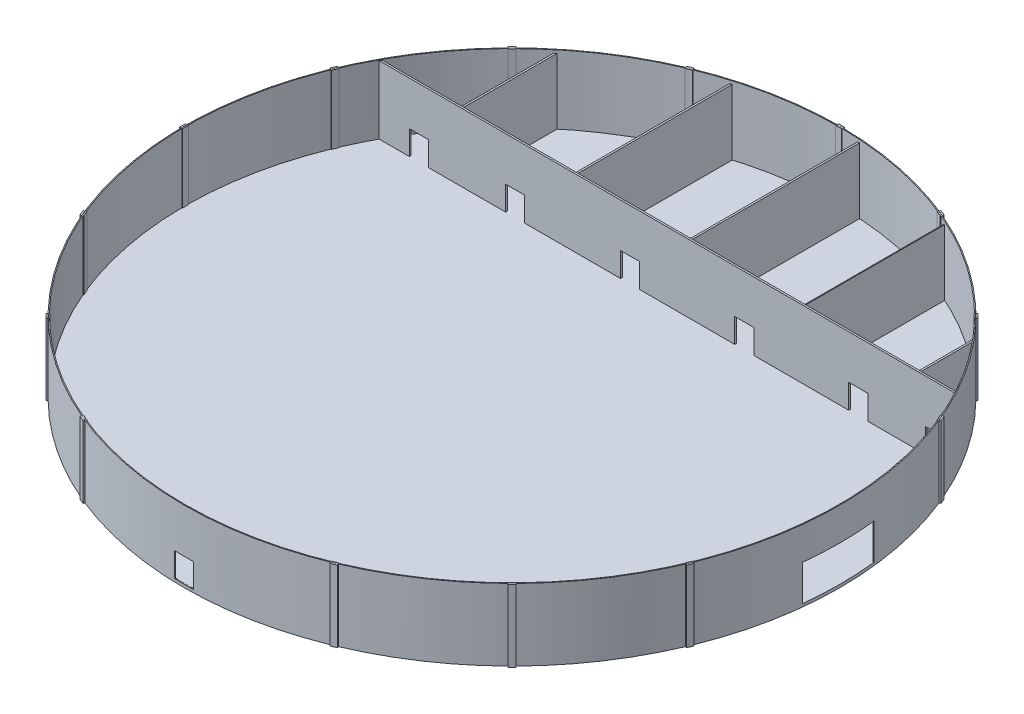
SolidWorks part; units mm, degrees
ref_plane "Front Plane" through (0, 0, 0) normal (0, 0, 1) x (1, 0, 0)
ref_plane "Top Plane" through (0, 0, 0) normal (0, 1, 0) x (1, 0, 0)
ref_plane "Right Plane" through (0, 0, 0) normal (1, 0, 0) x (0, 0, -1)
sketch "Sketch1" plane through (0, 0, 0) normal (0, 1, 0) x (1, 0, 0)
  circle A0 centre (0, 0) radius 27500
  dimension "D1" = 55000
extrude "Boss-Extrude2" add sketch "Sketch1" along normal blind 6000
sketch "Sketch2" plane through (0, 6000, 0) normal (0, 1, 0) x (1, 0, 0)
  circle A2 centre (0, 0) radius 27425
  dimension "D1" = 54850
extrude "Cut-Extrude1" cut sketch "Sketch2" against normal blind 5750
sketch "Sketch3" plane through (0, 0, 0) normal (0, 1, 0) x (1, 0, 0)
ref_plane "Plane1" through (0, 0, 27500) normal (0, 0, 1) x (1, 0, 0)
sketch "Sketch5" plane through (0, 0, 27500) normal (0, 0, 1) x (1, 0, 0)
  line L0 (-808.8037, 252) -> (-808.8037, 2284)
  line L1 (791.1963, 252) -> (791.1963, 2284)
  line L2 (791.1963, 2284) -> (-808.8037, 2284)
  line L3 (-808.8037, 252) -> (791.1963, 252)
  line L4 (-27500, 0) -> (27500, 0) construction
  dimension "D1" = 2032
  dimension "D2" = 2032
  dimension "D3" = 1600
  dimension "D4" = 1600
  dimension "D5" = 252
extrude "Cut-Extrude4" cut sketch "Sketch5" against normal mid plane 2527
sketch "Sketch6" plane through (0, 250, 0) normal (0, 1, 0) x (1, 0, 0)
  line L0 (23976.2032, 13150) -> (24148.0978, 13000)
  line L1 (-24148.0978, 13000) -> (24148.0978, 13000)
  line L2 (-23976.2032, 13150) -> (-24148.0978, 13000)
  line L3 (-23976.2032, 13150) -> (23976.2032, 13150)
sketch "Sketch8" plane through (0, 0, 0) normal (0, 1, 0) x (1, 0, 0)
  line L0 (-7969.0277, 26241.6696) -> (-7969.0277, 13140)
  line L1 (-7817.0277, 26287.3487) -> (-7817.0277, 13150)
  line L2 (-17559.0277, 21066.8263) -> (-17407.0277, 21192.5933)
  line L3 (-17559.0277, 13140) -> (-17559.0277, 21066.8263)
  line L4 (11210.9723, 25028.8778) -> (11210.9723, 13140)
  line L5 (-17407.0277, 13140) -> (-17407.0277, 21192.5933)
  line L6 (20800.9723, 17823.2128) -> (20800.9723, 13140)
  line L7 (-17559.0277, 13140) -> (-17407.0277, 13140)
  line L8 (1620.9723, 27377.0538) -> (1620.9723, 13150)
  line L9 (1772.9723, 27367.6304) -> (1772.9723, 13140)
  line L10 (11279.4964, 24997.9242) -> (11279.4964, 13140)
  line L11 (20952.9723, 17694.733) -> (20952.9723, 13140)
  line L12 (-7969.0277, 13140) -> (-7817.0277, 13150)
  line L13 (-7969.0277, 26241.6696) -> (-7817.0277, 26287.3487)
  line L14 (1620.9723, 13150) -> (1772.9723, 13140)
  line L15 (1620.9723, 27377.0538) -> (1772.9723, 27367.6304)
  line L16 (20800.9723, 17823.2128) -> (20952.9723, 17694.733)
  line L17 (20800.9723, 13140) -> (20952.9723, 13140)
  line L18 (11210.9723, 25028.8778) -> (11279.4964, 24997.9242)
  line L19 (11210.9723, 13140) -> (11279.4964, 13140)
  point P25 (-3806.1852, 6581.1135)
extrude "Boss-Extrude5" add sketch "Sketch8" along normal blind 5750 separate body
ref_plane "Plane6" through (27500, 0, 0) normal (1, 0, 0) x (0, 0, -1)
sketch "Sketch9" plane through (27500, 0, 0) normal (1, 0, 0) x (0, 0, -1)
  line L0 (-3000, 250) -> (3000, 250)
  line L1 (-3000, 250) -> (-3000, 3250)
  line L2 (-3000, 3250) -> (3000, 3250)
  line L3 (3000, 3250) -> (3000, 250)
  line L4 (-27500, 0) -> (27500, 0) construction
  point P3 (0, 250)
  dimension "D1" = 6000
  dimension "D2" = 3000
  dimension "D3" = 250
extrude "Cut-Extrude5" cut sketch "Sketch9" against normal blind 5750
sketch "Sketch12" plane through (0, 250, 0) normal (0, 1, 0) x (1, 0, 0)
  circle A0 centre (0, 0) radius 4000
  dimension "D1" = 8000
ref_plane "Plane8" through (0, 0, -13150) normal (0, 0, 1) x (1, 0, 0)
sketch "Sketch14" plane through (0, 0, -13150) normal (0, 0, 1) x (1, 0, 0)
  line L4 (-13534.6251, 250) -> (-11934.6251, 250)
  line L5 (-13534.6251, 250) -> (-13534.6251, 2280)
  line L6 (-13534.6251, 2280) -> (-11934.6251, 2280)
  line L7 (-11934.6251, 2280) -> (-11934.6251, 250)
  point P11 (-12734.6251, 250)
  dimension "D2" = 1600
sketch "Sketch15" plane through (0, 0, -13150) normal (0, 0, 1) x (1, 0, 0)
  line L0 (-3895.7392, 250) -> (-3895.7392, 2280)
  line L1 (-3895.7392, 2280) -> (-2295.7392, 2280)
  line L2 (-3895.7392, 250) -> (-2295.7392, 250)
  line L3 (-2295.7392, 2280) -> (-2295.7392, 250)
  line L4 (15229.6207, 250) -> (15229.6207, 2280)
  line L6 (5671.8023, 250) -> (7271.8023, 250)
  line L7 (5671.8023, 250) -> (5671.8023, 2280)
  line L8 (5671.8023, 2280) -> (7271.8023, 2280)
  line L9 (7271.8023, 2280) -> (7271.8023, 250)
  line L10 (15229.6207, 250) -> (16829.6207, 250)
  line L11 (15229.6207, 2280) -> (16829.6207, 2280)
  line L13 (16829.6207, 2280) -> (16829.6207, 250)
  line L17 (21660.0555, 250) -> (23260.0555, 250)
  line L18 (21660.0555, 250) -> (21660.0555, 2280)
  line L19 (21660.0555, 2280) -> (23260.0555, 2280)
  line L20 (23260.0555, 2280) -> (23260.0555, 250)
  line L23 (-21606.5684, 250) -> (-20006.5684, 250)
  line L24 (-21606.5684, 250) -> (-21606.5684, 2280)
  line L25 (-21606.5684, 2280) -> (-20006.5684, 2280)
  line L26 (-20006.5684, 2280) -> (-20006.5684, 250)
  point P7 (-3095.7392, 250)
  point P12 (6471.8023, 250)
  point P17 (16029.6207, 250)
  point P18 (6471.8023, 250)
  point P23 (22460.0555, 250)
  point P33 (-20806.5684, 250)
  dimension "D1" = 2030
  dimension "D2" = 1600
  dimension "D3" = 2030
  dimension "D4" = 1600
  dimension "D5" = 2030
  dimension "D6" = 1600
  dimension "D7" = 1600
  dimension "D8" = 2030
  dimension "D9" = 1600
  dimension "D10" = 2030
extrude "Boss-Extrude9" add sketch "Sketch6" along normal blind 5700 separate body
extrude "Cut-Extrude13" cut sketch "Sketch15" against normal mid plane 1000
extrude "Cut-Extrude14" cut sketch "Sketch14" against normal mid plane 1000
sketch "Sketch20" plane through (0, 0, 0) normal (0, 1, 0) x (1, 0, 0)
  line L0 (-4500, -13750) -> (-4500, -11750)
  line L1 (-1500, -13750) -> (1500, -13750)
  line L2 (-1500, -13750) -> (-4500, -13750)
  line L3 (1500, -13750) -> (4500, -13750)
  line L4 (-4500, -11750) -> (-3900, -11750)
  line L5 (4500, -13750) -> (4500, -11750)
  line L6 (4500, -11750) -> (3900, -11750)
  line L7 (-1500, -13150) -> (1500, -13150)
  line L8 (1500, -13150) -> (2500, -13150)
  line L9 (-2500, -13150) -> (-1500, -13150)
  arc A0 (-3900, -11750) -> (-2500, -13150) centre (-2500, -11750) ccw
  arc A1 (3900, -11750) -> (2500, -13150) centre (2500, -11750) cw
  point P5 (0, -13750)
  dimension "D1" = 2000
  dimension "D2" = 3000
  dimension "D3" = 3000
  dimension "D4" = 3000
  dimension "D5" = 600
  dimension "D6" = 600
  dimension "D7" = 3000
  dimension "D8" = 600
ref_plane "Plane9" through (0, 0, -27500) normal (0, 0, 1) x (1, 0, 0)
sketch "Sketch21" plane through (0, 0, -27500) normal (0, 0, 1) x (1, 0, 0)
  line L0 (-250, 0) -> (250, 0)
  line L1 (250, 0) -> (250, 5997.7048)
  line L2 (250, 5997.7048) -> (-250, 5997.7048)
  line L3 (-250, 5997.7048) -> (-250, 0)
  point P3 (0, 0)
  dimension "D1" = 500
  dimension "D2" = 500
extrude "Boss-Extrude10" add sketch "Sketch21" along normal mid plane 250
sketch "Sketch22" plane through (0, 0, 0) normal (0, 0, 1) x (1, 0, 0)
  line L0 (0, 0) -> (0, 6000)
  dimension "D1" = 6000
ref_axis "Axis1" through (0, 0, 0) along (0, 1, 0)
pattern_circular "CirPattern1" count 16 over 360 about axis through (0, 0, 0) along (0, 1, 0) skipping 4, 8 of "Boss-Extrude10" reverse direction yes
